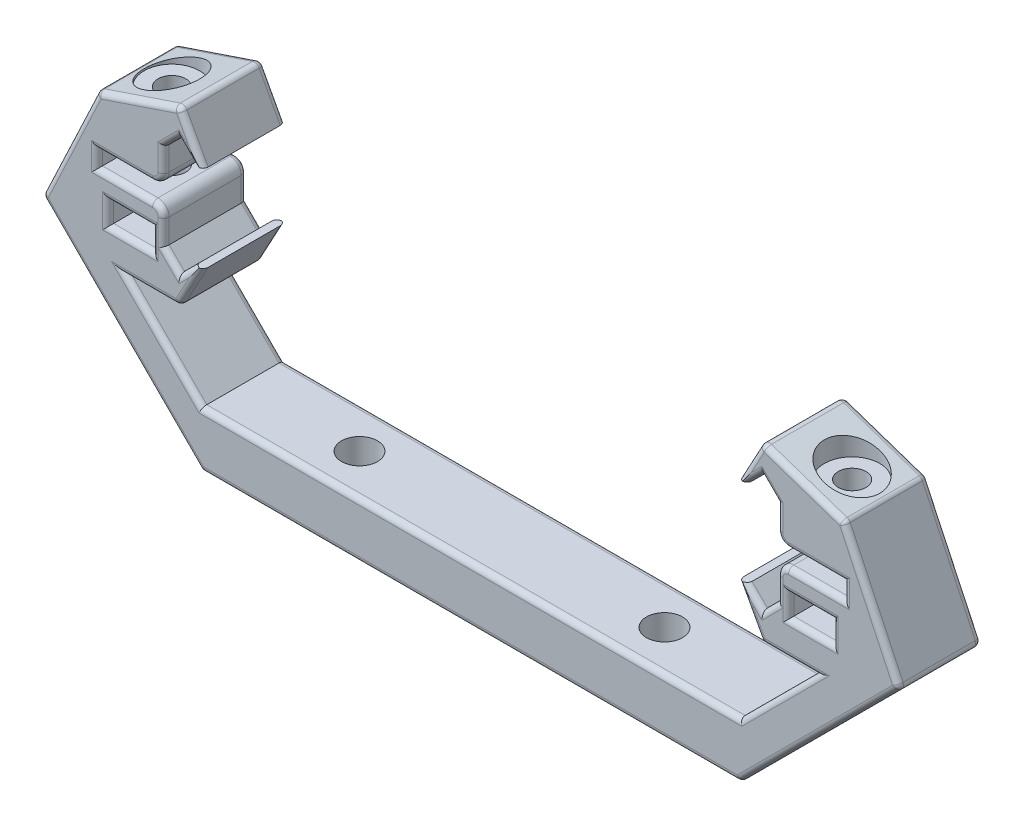
SolidWorks part; units mm, degrees
ref_plane "Front Plane" through (0, 0, 0) normal (0, 0, 1) x (1, 0, 0)
ref_plane "Top Plane" through (0, 0, 0) normal (0, 1, 0) x (1, 0, 0)
ref_plane "Right Plane" through (0, 0, 0) normal (1, 0, 0) x (0, 0, -1)
sketch "Sketch1" plane through (0, 0, 0) normal (0, 0, 1) x (1, 0, 0)
  line L0 (48.5324, 5) -> (67.3324, 23.8)
  line L1 (-48.5324, -5) -> (48.5324, -5)
  line L2 (0, -5) -> (0, 5)
  line L3 (-48.5324, 5) -> (48.5324, 5)
  line L4 (48.5324, -5) -> (48.5324, 5)
  line L5 (0, -5) -> (48.5324, 5) construction
  line L6 (0, 5) -> (48.5324, -5) construction
  line L7 (48.5324, -5) -> (77.3324, 23.8)
  line L8 (67.3324, 23.8) -> (77.3324, 23.8)
  line L9 (55.3324, 42.23) -> (52.5624, 45)
  line L12 (77.3324, 23.8) -> (67.3324, 23.8)
  line L13 (67.3324, 45) -> (67.3324, 23.8)
  line L14 (67.3324, 45) -> (77.3324, 23.8)
  line L15 (55.3324, 45) -> (67.3324, 45) construction
  line L19 (67.3324, 23.8) -> (67.3324, 45)
  line L20 (52.5624, 45) -> (49.7924, 42.23)
  line L21 (55.3324, 45) -> (49.7924, 45) construction
  line L22 (49.7924, 45) -> (49.7924, 42.23) construction
  line L23 (55.3324, 26.57) -> (52.5624, 23.8)
  line L24 (52.5624, 23.8) -> (49.7924, 26.57)
  line L25 (55.3324, 23.8) -> (49.7924, 23.8) construction
  line L26 (49.7924, 26.57) -> (49.7924, 23.8) construction
  line L27 (55.3324, 45) -> (55.3324, 42.23)
  line L28 (55.3324, 42.23) -> (55.3324, 26.57)
  line L29 (55.3324, 26.57) -> (55.3324, 23.8) construction
  line L30 (49.7924, 26.57) -> (48.2924, 26.57)
  line L31 (48.2924, 42.23) -> (52.5, 50)
  line L32 (49.7924, 42.23) -> (48.2924, 42.23)
  line L33 (48.2924, 26.57) -> (52.5, 18.8)
  line L34 (55.3324, 34.4) -> (67.3324, 34.4) construction
  line L35 (55.3324, 32.9) -> (67.3324, 32.9)
  line L36 (55.3324, 35.9) -> (67.3324, 35.9)
  line L37 (52.5, 18.8) -> (52.5, 23.8) construction
  line L38 (52.5, 50) -> (52.5, 45) construction
  line L40 (52.5, 50) -> (67.3324, 45)
  line L41 (67.3324, 32.9) -> (67.3324, 23.8)
  line L42 (67.3324, 32.9) -> (67.3324, 23.8)
  line L43 (52.5, 18.8) -> (62.3324, 18.8)
  line L44 (57.3324, 32.9) -> (57.3324, 24.9) construction
  line L45 (57.3324, 24.9) -> (65.3324, 24.9)
  line L46 (65.3324, 24.9) -> (65.3324, 32.9) construction
  line L47 (57.3324, 24.9) -> (57.3324, 28.9)
  line L48 (57.3324, 28.9) -> (65.3324, 28.9)
  line L49 (65.3324, 28.9) -> (65.3324, 24.9)
  line L50 (0, -55) -> (0, 55) construction
  line L51 (-65.3324, 24.9) -> (-65.3324, 32.9) construction
  line L52 (-57.3324, 32.9) -> (-57.3324, 24.9) construction
  line L53 (-52.5, 50) -> (-52.5, 45) construction
  line L54 (-52.5, 18.8) -> (-52.5, 23.8) construction
  line L55 (-55.3324, 34.4) -> (-67.3324, 34.4) construction
  line L56 (-55.3324, 26.57) -> (-55.3324, 23.8) construction
  line L57 (-49.7924, 26.57) -> (-49.7924, 23.8) construction
  line L58 (-55.3324, 23.8) -> (-49.7924, 23.8) construction
  line L59 (-49.7924, 45) -> (-49.7924, 42.23) construction
  line L60 (-55.3324, 45) -> (-49.7924, 45) construction
  line L61 (-55.3324, 45) -> (-67.3324, 45) construction
  line L62 (0, 5) -> (-48.5324, -5) construction
  line L63 (0, -5) -> (-48.5324, 5) construction
  line L64 (-65.3324, 28.9) -> (-65.3324, 24.9)
  line L65 (-57.3324, 28.9) -> (-65.3324, 28.9)
  line L66 (-57.3324, 24.9) -> (-57.3324, 28.9)
  line L67 (-57.3324, 24.9) -> (-65.3324, 24.9)
  line L68 (-52.5, 18.8) -> (-62.3324, 18.8)
  line L69 (-67.3324, 32.9) -> (-67.3324, 23.8)
  line L70 (-67.3324, 32.9) -> (-67.3324, 23.8)
  line L71 (-52.5, 50) -> (-67.3324, 45)
  line L72 (-55.3324, 35.9) -> (-67.3324, 35.9)
  line L73 (-55.3324, 32.9) -> (-67.3324, 32.9)
  line L74 (-48.2924, 26.57) -> (-52.5, 18.8)
  line L75 (-49.7924, 42.23) -> (-48.2924, 42.23)
  line L76 (-48.2924, 42.23) -> (-52.5, 50)
  line L77 (-49.7924, 26.57) -> (-48.2924, 26.57)
  line L78 (-55.3324, 42.23) -> (-55.3324, 26.57)
  line L79 (-55.3324, 45) -> (-55.3324, 42.23)
  line L80 (-52.5624, 23.8) -> (-49.7924, 26.57)
  line L81 (-55.3324, 26.57) -> (-52.5624, 23.8)
  line L82 (-52.5624, 45) -> (-49.7924, 42.23)
  line L83 (-67.3324, 23.8) -> (-67.3324, 45)
  line L84 (-67.3324, 45) -> (-77.3324, 23.8)
  line L85 (-67.3324, 45) -> (-67.3324, 23.8)
  line L86 (-77.3324, 23.8) -> (-67.3324, 23.8)
  line L87 (-55.3324, 42.23) -> (-52.5624, 45)
  line L88 (-67.3324, 23.8) -> (-77.3324, 23.8)
  line L89 (-48.5324, -5) -> (-77.3324, 23.8)
  line L90 (-48.5324, -5) -> (-48.5324, 5)
  line L91 (-48.5324, 5) -> (-67.3324, 23.8)
  point P0 (24.2662, 0)
  point P5 (0, 0)
  point P28 (52.5624, 45)
  point P30 (52.5624, 23.8)
  point P41 (61.3324, 24.9)
  point P81 (-24.2662, 0)
  dimension "D1" = 135
  dimension "D2" = 10
  dimension "D3" = 21.2
  dimension "D4" = 40
  dimension "D5" = 52.5
  dimension "D6" = 8
  dimension "D7" = 1.5
  dimension "D8" = 12
  dimension "D9" = 1.5
  dimension "D10" = 5.54
  dimension "D11" = 2.77
  dimension "D12" = 1.5
  dimension "D13" = 5
  dimension "D14" = 6
  dimension "D15" = 8
  dimension "D16" = 4
extrude "Boss-Extrude1" add sketch "Sketch1" along normal blind 7.5 and the other way blind 7.5 contours L1 L4 L3 L2 | L8 L0 L4 L7 | L14 L13 L19 L8 | L19 L35 L28 L23 L24 L30 L33 | L40 L31 L32 L20 L9 L28 L36 L13 | L90 L1 L2 L3 | L90 L91 L86 L89 | L91 L68 L74 L77 L80 L81 L78 L73 L69 L66 L67 L64 L65 | L84 L86 L69 L83 | L87 L82 L75 L76 L71 L83 L72 L78 region at (24.2662, 0, 0) region at (60.6075, 11.7249, 0) region at (57.4162, 19.0369, 0) region at (-24.2662, 0, 0) region at (70.6658, 30.8667, 0) region at (-60.6075, 11.7249, 0) region at (-64.6649, 21.4675, 0) region at (59.475, 42.3299, 0) region at (-70.6658, 30.8667, 0) region at (-59.475, 42.3299, 0)
sketch "Sketch2" plane through (0, 35.9, 0) normal (0, -1, 0) x (1, 0, 0)
  line L0 (55.3324, 7.5) -> (55.3324, -7.5) construction
  line L1 (55.3324, 7.5) -> (67.3324, 7.5) construction
  circle A0 centre (61.3324, 0) radius 2.5
  point P4 (55.3324, 0)
  dimension "D1" = 5
  dimension "D2" = 6
  dimension "D3" = 7.5
extrude "Cut-Extrude1" cut sketch "Sketch2" against normal through all
extrude "Cut-Extrude2" cut sketch "Sketch2<2>" along normal blind 16
sketch "Sketch2<2>" plane through (0, 35.9, 0) normal (0, -1, 0) x (1, 0, 0) same geometry as "Sketch2"
sketch "Sketch5" plane through (0, 5, 0) normal (0, 1, 0) x (1, 0, 0)
  line L0 (-27.5, 7.5) -> (-27.5, -7.5) construction
  line L1 (-48.5324, 7.5) -> (48.5324, 7.5) construction
  line L2 (-48.5324, -7.5) -> (48.5324, -7.5) construction
  circle A0 centre (-27.5, 0) radius 3.25
  circle A1 centre (27.5, 0) radius 3.25
  point P4 (-27.5, 0)
  point P5 (0, 7.5)
  dimension "D2" = 6.5
  dimension "D1" = 55
  dimension "D3" = 27.5
extrude "Cut-Extrude4" cut sketch "Sketch5" along normal up to next from surface starting at face at (0, -5, 0)
sketch "Sketch6" plane through (0, 35.9, 0) normal (0, -1, 0) x (1, 0, 0)
  line L0 (-55.3324, 7.5) -> (-55.3324, -7.5) construction
  line L1 (-55.3324, 7.5) -> (-67.3324, 7.5) construction
  circle A0 centre (-61.3324, 0) radius 2.5
  dimension "D1" = 5
  dimension "D2" = 6
  dimension "D3" = 7.5
extrude "Cut-Extrude5" cut sketch "Sketch6" against normal through all
extrude "Cut-Extrude6" cut sketch "Sketch6<4>" along normal blind 16
sketch "Sketch6<4>" plane through (0, 35.9, 0) normal (0, -1, 0) x (1, 0, 0) same geometry as "Sketch6"
sketch "Sketch4" plane through (0, 0, 0) normal (0, 1, 0) x (1, 0, 0)
  circle A0 centre (61.3324, 0) radius 2.5
  circle A1 centre (61.3324, 0) radius 5
  circle A2 centre (-61.3324, 0) radius 2.5
  circle A3 centre (-61.3324, 0) radius 5
  dimension "D1" = 5
  dimension "D2" = 10
extrude "Cut-Extrude3" cut sketch "Sketch4" against normal blind 5 from offset 50
fillet "Fillet24" radius 2 4 edges at (-55.3324, 35.9, 0) (-55.3324, 32.9, 0) (55.3324, 35.9, 0) (55.3324, 32.9, 0)
fillet "Fillet25" radius 1 102 edges at (77.3324, 23.8, 0) (67.3324, 45, 0) (-61.3324, 24.9, -7.5) (-65.3324, 26.9, -7.5) (-61.3324, 28.9, -7.5) (-57.3324, 26.9, -7.5) (65.3324, 26.9, -7.5) (61.3324, 24.9, -7.5) (57.3324, 26.9, -7.5) (61.3324, 28.9, -7.5) (-53.9474, 43.615, -7.5) (-51.1774, 43.615, -7.5) (-50.3962, 46.115, -7.5) (-59.9162, 47.5, -7.5) (-72.3324, 34.4, -7.5) (-62.9324, 9.4, -7.5) (0, -5, -7.5) (62.9324, 9.4, -7.5) (72.3324, 34.4, -7.5) (59.9162, 47.5, -7.5) (50.3962, 46.115, -7.5) (51.1774, 43.615, -7.5) (53.9474, 43.615, -7.5) (55.3324, 40.065, -7.5) (55.9182, 36.4858, -7.5) (62.3324, 35.9, -7.5) (67.3324, 34.4, -7.5) (62.3324, 32.9, -7.5) (55.9182, 32.3142, -7.5) (55.3324, 28.735, -7.5) (53.9474, 25.185, -7.5) (51.1774, 25.185, -7.5) (50.3962, 22.685, -7.5) (57.4162, 18.8, -7.5) (55.4324, 11.9, -7.5) (0, 5, -7.5) (-55.4324, 11.9, -7.5) (-57.4162, 18.8, -7.5) (-50.3962, 22.685, -7.5) (-51.1774, 25.185, -7.5) (-53.9474, 25.185, -7.5) (-55.3324, 28.735, -7.5) (-55.9182, 32.3142, -7.5) (-62.3324, 32.9, -7.5) (-67.3324, 34.4, -7.5) (-62.3324, 35.9, -7.5) (-55.9182, 36.4858, -7.5) (-55.3324, 40.065, -7.5) (-61.3324, 28.9, 7.5) (-65.3324, 26.9, 7.5) (-61.3324, 24.9, 7.5) (-57.3324, 26.9, 7.5) (57.3324, 26.9, 7.5) (61.3324, 24.9, 7.5) (65.3324, 26.9, 7.5) (61.3324, 28.9, 7.5) (-67.3324, 34.4, 7.5) (-62.3324, 32.9, 7.5) (-55.9182, 32.3142, 7.5) (-55.3324, 28.735, 7.5) (-53.9474, 25.185, 7.5) (-51.1774, 25.185, 7.5) (-50.3962, 22.685, 7.5) (-57.4162, 18.8, 7.5) (-55.4324, 11.9, 7.5) (0, 5, 7.5) (55.4324, 11.9, 7.5) (57.4162, 18.8, 7.5) (50.3962, 22.685, 7.5) (51.1774, 25.185, 7.5) (53.9474, 25.185, 7.5) (55.3324, 28.735, 7.5) (55.9182, 32.3142, 7.5) (62.3324, 32.9, 7.5) (67.3324, 34.4, 7.5) (62.3324, 35.9, 7.5) (55.9182, 36.4858, 7.5) (55.3324, 40.065, 7.5) (53.9474, 43.615, 7.5) (51.1774, 43.615, 7.5) (50.3962, 46.115, 7.5) (59.9162, 47.5, 7.5) (72.3324, 34.4, 7.5) (62.9324, 9.4, 7.5) (0, -5, 7.5) (-62.9324, 9.4, 7.5) (-72.3324, 34.4, 7.5) (-59.9162, 47.5, 7.5) (-50.3962, 46.115, 7.5) (-51.1774, 43.615, 7.5) (-53.9474, 43.615, 7.5) (-55.3324, 40.065, 7.5) (-55.9182, 36.4858, 7.5) (-62.3324, 35.9, 7.5) (-77.3324, 23.8, 0) (-48.5324, -5, 0) (48.5324, -5, 0) (-67.3324, 45, 0) (-52.5, 50, 0) (52.5, 50, 0) (52.5, 18.8, 0) (-52.5, 18.8, 0)
